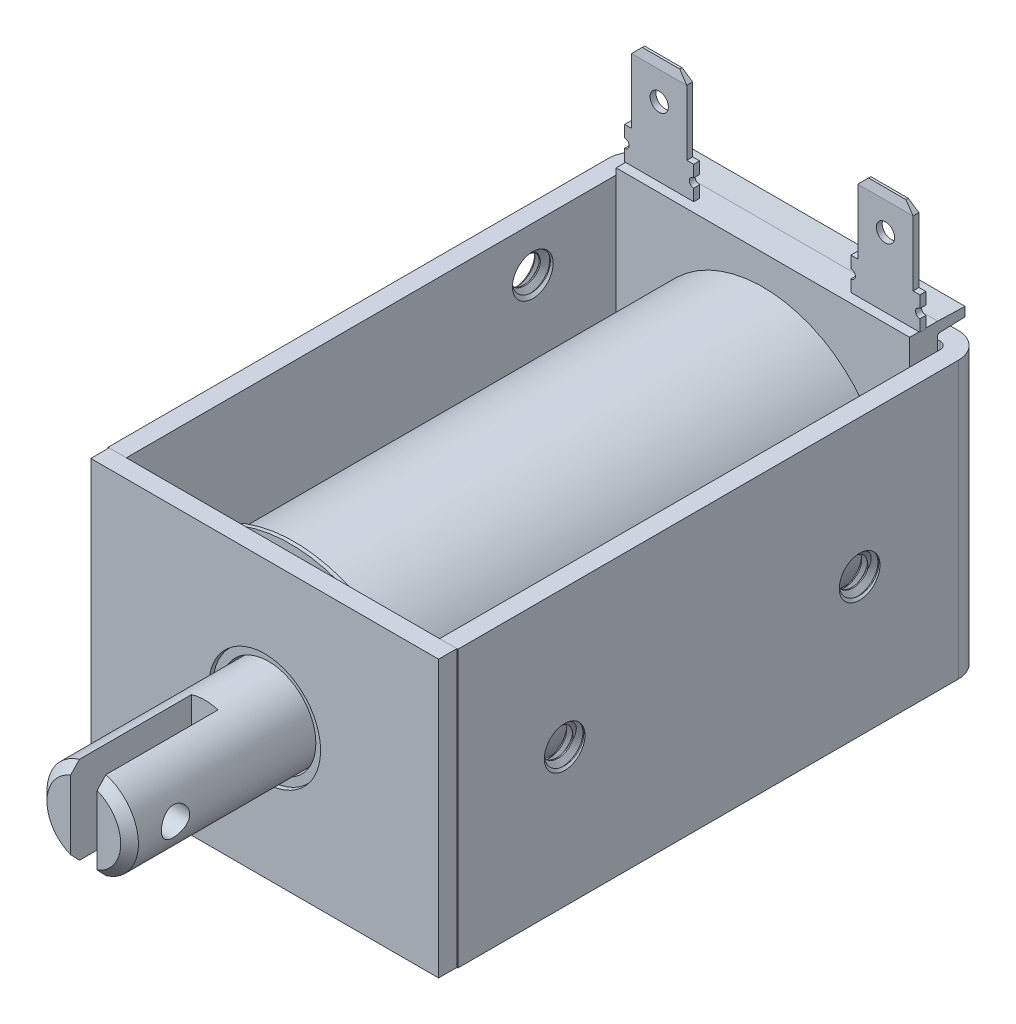
SolidWorks part; units mm, degrees
ref_plane "Front" through (0, 0, 0) normal (0, 0, 1) x (1, 0, 0)
ref_plane "Top" through (0, 0, 0) normal (0, 1, 0) x (1, 0, 0)
ref_plane "Right" through (0, 0, 0) normal (1, 0, 0) x (0, 0, -1)
sketch "Sketch1" plane through (0, 0, 0) normal (1, 0, 0) x (0, 0, -1)
  line L0 (0, 0) -> (46.8884, 0) construction
  line L1 (0, 0) -> (-15.5702, 0) construction
  line L2 (-15.5702, 3.937) -> (-15.5702, -3.937) construction
  line L4 (0, 11.8872) -> (0, -11.8872) construction
  line L6 (36.576, 8.0137) -> (36.576, 0) construction
  line L7 (15.9512, -8.0137) -> (15.9512, 0) construction
  circle A0 centre (36.576, 8.0137) radius 1.7526 construction
  circle A1 centre (15.9512, -8.0137) radius 1.7526 construction
  circle A2 centre (10.7696, 0) radius 1.7526 construction
  circle A3 centre (36.1696, 0) radius 1.7526 construction
  dimension "H" = 3.5052
  dimension "A" = 15.5702
  dimension "B" = 46.8884
  dimension "D" = 23.7744
  dimension "E" = 62.4586
  dimension "R" = 7.874
  dimension "G2" = 20.6248
  dimension "J1" = 16.0274
  dimension "K3" = 15.9512
  dimension "K4" = 10.3124
  dimension "G1" = 25.4
  dimension "K1" = 10.7696
  dimension "K2" = 10.7188
sketch "Sketch2" plane through (0, 0, 0) normal (0, 0, 1) x (1, 0, 0)
  line L0 (-14.9733, 0) -> (14.9733, 0) construction
  dimension "C" = 29.9466
sketch "Sketch3" plane through (0, 0, 0) normal (0, 1, 0) x (1, 0, 0)
  line L1 (-14.9733, 1.5748) -> (14.9733, 1.5748)
  line L2 (-14.9733, 1.5748) -> (-14.9733, 0)
  line L3 (-14.9733, 0) -> (14.9733, 0)
  line L4 (14.9733, 1.5748) -> (14.9733, 0)
  dimension "D1" = 1.5748
extrude "Boss-Extrude1" add sketch "Sketch3" along normal up to vertex (11.8872 mm away) and the other way up to vertex (11.8872 mm away) up to point (0, 11.8872, 0) other way up to point (0, -11.8872, 0)
sketch "Sketch4" plane through (0, 0, 0) normal (0, 0, -1) x (-1, 0, 0)
  circle A0 centre (0, 0) radius 4.8133
  dimension "D1" = 9.6266
extrude "Cut-Extrude1" cut sketch "Sketch4" along normal up to surface (1.5748 mm away) up to face at (0, 0, -1.5748)
sketch "Sketch5" plane through (0, 0, 0) normal (0, 1, 0) x (1, 0, 0)
  line L0 (-15.0622, 1.5748) -> (-15.0622, 44.6786)
  line L2 (-14.9733, 1.5748) -> (14.9733, 1.5748) construction
  line L5 (-12.8524, 46.8884) -> (12.8524, 46.8884)
  line L6 (15.0622, 44.6786) -> (15.0622, 1.5748)
  line L9 (15.0622, 1.5748) -> (13.4874, 1.5748)
  line L10 (13.4874, 1.5748) -> (13.4874, 44.6786)
  line L11 (12.8524, 45.3136) -> (-12.8524, 45.3136)
  line L12 (-13.4874, 44.6786) -> (-13.4874, 1.5748)
  line L13 (-13.4874, 1.5748) -> (-15.0622, 1.5748)
  line L14 (0, 46.8884) -> (0, 45.3136) construction
  arc A0 (-12.8524, 46.8884) -> (-15.0622, 44.6786) centre (-12.8524, 44.6786) ccw
  arc A1 (15.0622, 44.6786) -> (12.8524, 46.8884) centre (12.8524, 44.6786) ccw
  arc A2 (-12.8524, 45.3136) -> (-13.4874, 44.6786) centre (-12.8524, 44.6786) ccw
  arc A3 (13.4874, 44.6786) -> (12.8524, 45.3136) centre (12.8524, 44.6786) ccw
  dimension "D3" = 30.1244
  dimension "D1" = 2.2098
  dimension "D2" = 1.5748
extrude "Boss-Extrude2" add sketch "Sketch5" along normal up to vertex (11.8872 mm away) and the other way up to vertex (11.8872 mm away) separate body up to point (0, 11.8872, 0) other way up to point (0, -11.8872, 0)
sketch "Sketch6" plane through (0, 0, -46.8884) normal (0, 0, -1) x (-1, 0, 0)
  line L0 (14.9733, 0) -> (-14.9733, 0) construction
  circle A0 centre (0, 0) radius 2.1082
  dimension "D1" = 4.2164
extrude "Cut-Extrude2" cut sketch "Sketch6" against normal up to surface (1.5748 mm away) up to face at (0, 0, -45.3136)
sketch "Sketch7" plane through (0, 0, 0) normal (1, 0, 0) x (0, 0, -1)
  line L0 (36.1696, 0) -> (10.7696, 0) construction
  circle A0 centre (36.1696, 0) radius 1.7526 construction
  circle A3 centre (36.1696, 0) radius 1.7526
  dimension "D1" = 25.4
extrude "Boss-Extrude3" add sketch "Sketch7" along normal up to surface (1.5748 mm away) from surface at 13.4874 separate body up to face at (15.0622, 0, -23.1267) starting at face at (13.4874, 0, -23.1267)
sketch "Sketch8" plane through (13.4874, 0, 0) normal (-1, 0, 0) x (0, 0, 1)
  circle A1 centre (-36.1696, 0) radius 1.7526
  circle A2 centre (-36.1696, 0) radius 1.7526
  point P0 (-36.1696, 1.7526)
  dimension "D1" = 0
curve "Helix/Spiral1" pitch 0.7937 height 2.3177 turns 2.92 parameters "Pitch"=0.7937
ref_plane "Plane1" through (0, 0, -36.1696) normal (0, 0, 1) x (1, 0, 0)
sketch "Sketch9" plane through (0, 0, -36.1696) normal (0, 0, 1) x (1, 0, 0)
  line L0 (12.7433, 1.8385) -> (13.537, 1.8385) construction
  line L1 (13.537, 1.8385) -> (13.1401, 1.1511) construction
  line L2 (13.1401, 1.1511) -> (12.7433, 1.8385) construction
  line L3 (13.1897, 1.237) -> (13.0905, 1.237) construction
  line L4 (13.4874, 1.7526) -> (12.7929, 1.7526) construction
  line L5 (13.0905, 1.237) -> (13.1897, 1.237)
  line L6 (13.1897, 1.237) -> (13.5122, 1.7956)
  line L7 (13.5122, 1.7956) -> (12.7681, 1.7956)
  line L8 (12.7681, 1.7956) -> (13.0905, 1.237)
  line L9 (13.1401, 1.1511) -> (13.1401, 1.237) construction
  line L10 (13.1401, 1.7526) -> (13.1401, 1.8385) construction
  point P15 (13.1401, 1.7956)
  dimension "D1" = 0.7937
  dimension "D2" = 0.0992
sweep "Cut-Sweep1" cut profiles "Sketch9" path "Helix/Spiral1" align with end faces yes
sketch "Sketch10" plane through (13.4874, 0, 0) normal (-1, 0, 0) x (0, 0, 1)
  circle A1 centre (-36.1696, 0) radius 1.7526 construction
  circle A2 centre (-36.1696, 0) radius 1.7526
extrude "Boss-Extrude4" add sketch "Sketch10" against normal blind 0.7937 draft 45
sketch "Sketch11" plane through (15.0622, 0, 0) normal (1, 0, 0) x (0, 0, -1)
  circle A1 centre (36.1696, 0) radius 1.7526
  circle A2 centre (36.1696, 0) radius 1.7526
  dimension "D1" = 0
extrude "Boss-Extrude5" add sketch "Sketch11" against normal blind 0.7937 draft 45
pattern_linear "LPattern1" count 2 spacing 25.4 along (0, 0, 1) of bodies 165
sketch "Sketch20" plane through (0, 0, 0) normal (1, 0, 0) x (0, 0, -1)
  line L0 (36.576, 8.0137) -> (15.9512, -8.0137) construction
  circle A0 centre (36.576, 8.0137) radius 1.7526 construction
  circle A1 centre (36.576, 8.0137) radius 1.7526
  dimension "D1" = 26.1201
extrude "Boss-Extrude9" add sketch "Sketch20" against normal up to surface (1.5748 mm away) from surface at -13.4874 separate body up to face at (-15.0622, 0, -23.1267) starting at face at (-13.4874, 0, -23.1267)
sketch "Sketch21" plane through (-13.4874, 0, 0) normal (1, 0, 0) x (0, 0, -1)
  circle A1 centre (36.576, 8.0137) radius 1.7526
  circle A2 centre (36.576, 8.0137) radius 1.7526
  point P0 (36.576, 9.7663)
  dimension "D1" = 0
curve "Helix/Spiral2" pitch 0.7937 height 2.3685 turns 2.984 parameters "Pitch"=0.7937
ref_plane "Plane2" through (0, 0, -36.576) normal (0, 0, 1) x (1, 0, 0)
sketch "Sketch22" plane through (0, 0, -36.576) normal (0, 0, 1) x (1, 0, 0)
  line L0 (-13.537, 9.8522) -> (-12.7433, 9.8522) construction
  line L1 (-12.7433, 9.8522) -> (-13.1401, 9.1648) construction
  line L2 (-13.1401, 9.1648) -> (-13.537, 9.8522) construction
  line L3 (-13.1897, 9.2507) -> (-13.0905, 9.2507) construction
  line L4 (-13.4874, 9.7663) -> (-12.7929, 9.7663) construction
  line L5 (-13.1401, 9.1648) -> (-13.1401, 9.2507) construction
  line L6 (-13.1401, 9.7663) -> (-13.1401, 9.8522) construction
  line L7 (-13.1897, 9.2507) -> (-13.0905, 9.2507)
  line L8 (-13.0905, 9.2507) -> (-12.7681, 9.8093)
  line L9 (-12.7681, 9.8093) -> (-13.5122, 9.8093)
  line L10 (-13.5122, 9.8093) -> (-13.1897, 9.2507)
  point P13 (-13.1401, 9.8093)
  dimension "D1" = 0.7937
  dimension "D2" = 0.0992
sweep "Cut-Sweep2" cut profiles "Sketch22" path "Helix/Spiral2" align with end faces yes
sketch "Sketch23" plane through (-13.4874, 0, 0) normal (1, 0, 0) x (0, 0, -1)
  circle A1 centre (36.576, 8.0137) radius 1.7526
  circle A2 centre (36.576, 8.0137) radius 1.7526
  dimension "D1" = 0
extrude "Boss-Extrude10" add sketch "Sketch23" against normal blind 0.7937 draft 45
sketch "Sketch24" plane through (-15.0622, 0, 0) normal (-1, 0, 0) x (0, 0, 1)
  circle A1 centre (-36.576, 8.0137) radius 1.7526
  circle A2 centre (-36.576, 8.0137) radius 1.7526
  dimension "D1" = 0
extrude "Boss-Extrude11" add sketch "Sketch24" against normal blind 0.7937 draft 45
pattern_linear "LPattern2" count 2 spacing 26.1201 along (0, -0.6136, 0.7896) of bodies 186
combine bodies "Combine1" operation type subtract main body 133 bodies to subtract 165 178 187 186
sketch "Sketch12" plane through (0, 0, -45.3136) normal (0, 0, 1) x (1, 0, 0)
  line L0 (0, -11.8745) -> (0, 0) construction
  line L1 (-12.6365, 13.2715) -> (12.6365, 13.2715)
  line L2 (-12.6365, 13.2715) -> (-12.6365, -8.6995)
  line L3 (-9.4615, -11.8745) -> (9.4615, -11.8745)
  line L4 (12.6365, 13.2715) -> (12.6365, -8.6995)
  line L6 (-12.8524, -11.8872) -> (12.8524, -11.8872) construction
  circle A0 centre (0, 0) radius 4.0767
  arc A1 (-12.6365, -8.6995) -> (-9.4615, -11.8745) centre (-9.4615, -8.6995) ccw
  arc A2 (9.4615, -11.8745) -> (12.6365, -8.6995) centre (9.4615, -8.6995) ccw
  dimension "D2" = 8.1534
  dimension "D4" = 3.175
  dimension "D1" = 25.273
  dimension "D3" = 25.146
  dimension "D5" = 0.0127
extrude "Boss-Extrude6" add sketch "Sketch12" along normal blind 2.413 separate body
sketch "Sketch13" plane through (0, 0, 0) normal (1, 0, 0) x (0, 0, -1)
  line L0 (45.3136, 13.2715) -> (47.6758, 13.1952)
  line L1 (47.6758, 13.1952) -> (47.6758, 12.4078)
  line L2 (47.6758, 12.4078) -> (45.4611, 12.3363)
  line L3 (45.3136, 12.1839) -> (45.3136, 13.2715)
  line L4 (47.6758, 12.8015) -> (45.3136, 12.8015) construction
  arc A0 (45.4611, 12.3363) -> (45.3136, 12.1839) centre (45.466, 12.1839) ccw
  dimension "D1" = 0.1524
  dimension "D2" = 2.3622
  dimension "D3" = 3.7
  dimension "D4" = 1.85
  dimension "D5" = 0.7874
extrude "Boss-Extrude7" add sketch "Sketch13" along normal up to vertex (12.6365 mm away) and the other way up to vertex (12.6365 mm away) up to point (12.6365, 13.2715, -45.3136) other way up to point (-12.6365, 13.2715, -45.3136)
sketch "Sketch14" plane through (0, 0, 0) normal (1, 0, 0) x (0, 0, -1)
  line L0 (0, 0) -> (42.9006, 0) construction
  line L1 (0, 11.8872) -> (0, -11.8872) construction
  line L2 (42.9006, -8.6995) -> (42.9006, 13.2715) construction
  line L3 (42.9006, 4.0767) -> (42.9006, 10.7061)
  line L4 (42.9006, 10.7061) -> (2.54, 10.7061)
  line L5 (2.54, 10.7061) -> (2.54, 11.8999)
  line L6 (2.54, 11.8999) -> (2.2098, 11.8999)
  line L7 (2.2098, 11.8999) -> (2.2098, 9.525)
  line L8 (0.3302, 4.0767) -> (42.9006, 4.0767)
  line L12 (2.2098, 9.525) -> (1.905, 9.525)
  line L13 (1.905, 9.525) -> (1.905, 4.7663)
  line L14 (1.905, 4.7663) -> (0.3302, 4.7663)
  line L15 (0.3302, 4.7663) -> (0.3302, 4.0767)
  dimension "D1" = 40.3606
  dimension "D2" = 0.3302
  dimension "D3" = 0.3048
  dimension "D4" = 1.5748
  dimension "D5" = 21.4122
  dimension "D6" = 23.7998
  dimension "D7" = 19.05
  dimension "D8" = 9.5326
revolve "Revolve1" add sketch "Sketch14" angle 360 mid plane about L0
sketch "Sketch15" plane through (0, 0, -42.9006) normal (0, 0, 1) x (1, 0, 0)
  line L0 (12.6365, 13.2715) -> (-12.6365, 13.2715) construction
  line L1 (6.7691, 13.2715) -> (12.7127, 13.2715)
  line L2 (8.128, 22.4155) -> (7.366, 21.6535)
  line L3 (8.128, 22.4155) -> (11.3538, 22.4155)
  line L4 (12.7127, 13.2715) -> (12.7127, 14.2875)
  line L5 (0, 13.2715) -> (0, 22.4155) construction
  line L6 (7.366, 21.6535) -> (7.366, 16.0655)
  line L7 (7.366, 16.0655) -> (6.7691, 16.0655)
  line L8 (6.7691, 15.0495) -> (6.7691, 16.0655)
  line L9 (11.3538, 22.4155) -> (12.1158, 21.6535)
  line L10 (12.1158, 21.6535) -> (12.1158, 16.0655)
  line L11 (12.1158, 16.0655) -> (12.7127, 16.0655)
  line L12 (6.7691, 13.2715) -> (6.7691, 14.2875)
  line L13 (12.7127, 15.0495) -> (12.7127, 16.0655)
  line L14 (9.7409, 13.2715) -> (9.7409, 22.4155) construction
  line L15 (-12.7127, 13.2715) -> (-12.7127, 14.2875)
  line L16 (-12.7127, 15.0495) -> (-12.7127, 16.0655)
  line L17 (-12.1158, 16.0655) -> (-12.7127, 16.0655)
  line L18 (-12.1158, 21.6535) -> (-12.1158, 16.0655)
  line L19 (-11.3538, 22.4155) -> (-12.1158, 21.6535)
  line L20 (-8.128, 22.4155) -> (-11.3538, 22.4155)
  line L21 (-6.7691, 13.2715) -> (-6.7691, 14.2875)
  line L22 (-6.7691, 15.0495) -> (-6.7691, 16.0655)
  line L23 (-7.366, 16.0655) -> (-6.7691, 16.0655)
  line L24 (-7.366, 21.6535) -> (-7.366, 16.0655)
  line L25 (-8.128, 22.4155) -> (-7.366, 21.6535)
  line L26 (-6.7691, 13.2715) -> (-12.7127, 13.2715)
  line L27 (12.7127, 16.0655) -> (12.7127, 13.2715) construction
  arc A0 (6.7691, 15.0495) -> (6.7691, 14.2875) centre (6.7691, 14.6685) cw
  arc A1 (12.7127, 15.0495) -> (12.7127, 14.2875) centre (12.7127, 14.6685) ccw
  circle A2 centre (9.7409, 19.2405) radius 0.7874
  circle A3 centre (-9.7409, 19.2405) radius 0.7874
  arc A4 (-12.7127, 15.0495) -> (-12.7127, 14.2875) centre (-12.7127, 14.6685) cw
  arc A5 (-6.7691, 15.0495) -> (-6.7691, 14.2875) centre (-6.7691, 14.6685) ccw
  dimension "D3" = 1.5748
  dimension "D10" = 0.381
  dimension "D1" = 9.144
  dimension "D2" = 0.762
  dimension "D4" = 4.7498
  dimension "D5" = 0.762
  dimension "D6" = 5.9436
  dimension "D7" = 6.35
  dimension "D8" = 19.4818
  dimension "D9" = 3.175
extrude "Boss-Extrude8" add sketch "Sketch15" against normal blind 0.508 from offset 0.8128 offset against normal yes
sketch "Sketch16" plane through (0, 0, 0) normal (1, 0, 0) x (0, 0, -1)
  line L0 (43.7134, 22.4155) -> (43.7134, 21.6535)
  line L1 (43.7134, 21.6535) -> (43.8658, 22.4155)
  line L2 (44.2214, 22.4155) -> (43.7134, 22.4155) construction
  line L3 (43.8658, 22.4155) -> (43.7134, 22.4155)
  line L4 (44.069, 22.4155) -> (44.2214, 21.6535)
  line L5 (44.2214, 21.6535) -> (44.2214, 22.4155)
  line L6 (44.2214, 22.4155) -> (44.069, 22.4155)
  dimension "D1" = 0.1524
extrude "Cut-Extrude3" cut sketch "Sketch16" against normal through all and the other way through all
sketch "Sketch17" plane through (0, 0, 0) normal (1, 0, 0) x (0, 0, -1)
  line L0 (-15.5702, 0) -> (47.752, 0) construction
  line L1 (-15.5702, 0) -> (47.752, 0)
  line L2 (-15.5702, 0) -> (-15.5702, 3.175)
  line L3 (-14.8082, 3.937) -> (31.8262, 3.937)
  line L4 (47.752, 2.032) -> (47.752, 0)
  line L6 (45.212, 3.9751) -> (45.212, 2.032)
  line L7 (-14.8082, 3.937) -> (-15.5702, 3.175)
  line L8 (-14.8082, 3.937) -> (-15.5702, 3.937) construction
  line L9 (-15.5702, 3.937) -> (-15.5702, 3.175) construction
  line L10 (45.212, 2.032) -> (47.752, 2.032)
  line L11 (31.8262, 3.937) -> (31.8262, 3.9751)
  line L12 (31.8262, 3.9751) -> (45.212, 3.9751)
  dimension "D1" = 2.54
  dimension "D2" = 13.3858
  dimension "D3" = 0.762
  dimension "D4" = 63.3222
  dimension "D5" = 7.9502
  dimension "D6" = 4.064
revolve "Revolve2" add sketch "Sketch17" angle 360 mid plane about L0
sketch "Sketch18" plane through (0, 0, 0) normal (0, 1, 0) x (1, 0, 0)
  line L1 (-1.143, -15.5702) -> (1.143, -15.5702)
  line L2 (-1.143, -15.5702) -> (-1.143, -5.1562)
  line L3 (-1.143, -5.1562) -> (1.143, -5.1562)
  line L4 (1.143, -15.5702) -> (1.143, -5.1562)
  dimension "D1" = 2.286
  dimension "D2" = 10.414
extrude "Cut-Extrude4" cut sketch "Sketch18" along normal up to vertex (3.937 mm away) and the other way up to vertex (3.937 mm away) up to point (0, 3.937, 15.5702) other way up to point (0, -3.937, 15.5702)
sketch "Sketch19" plane through (0, 0, 0) normal (1, 0, 0) x (0, 0, -1)
  line L0 (-15.5702, 0) -> (-11.6078, 0) construction
  circle A0 centre (-11.6078, 0) radius 1.2192
  dimension "D1" = 2.4384
  dimension "D2" = 3.9624
extrude "Cut-Extrude5" cut sketch "Sketch19" against normal through all and the other way through all
sketch "SketchX" plane through (0, 0, 0) normal (1, 0, 0) x (0, 0, -1)
  line L2 (-28.2702, -2.9621) -> (-28.2702, 2.9621)
  line L13 (-15.5702, 0) -> (-11.6078, 0) construction
  line L15 (-28.2702, 2.9621) -> (-27.5082, 3.7674)
  line L16 (-17.8562, 3.937) -> (-5.1562, 3.937)
  line L17 (-28.2702, -2.9621) -> (-27.5082, -3.7674)
  line L18 (-17.8562, -3.937) -> (-5.1562, -3.937)
  line L26 (-27.5082, 3.7674) -> (-17.8562, 3.7674)
  line L27 (-17.8562, 3.7674) -> (-17.8562, 3.937)
  line L28 (-27.5082, -3.7674) -> (-17.8562, -3.7674)
  line L29 (-17.8562, -3.7674) -> (-17.8562, -3.937)
  line L30 (-24.3078, 0) -> (-28.2702, 0) construction
  line L32 (-14.8082, 3.7674) -> (-5.1562, 3.7674) construction
  line L33 (-5.1562, -3.7674) -> (-14.8082, -3.7674) construction
  line L35 (-5.1562, 3.937) -> (-5.1562, 3.7674) construction
  line L36 (31.8262, 3.937) -> (-5.1562, 3.937) construction
  circle A0 centre (-24.3078, 0) radius 1.2192
  circle A1 centre (-11.6078, 0) radius 1.2192 construction
  dimension "D1" = 0.762
  dimension "Stroke" = 12.7
equation "\"D1@Sketch9\" = \"Pitch@Helix/Spiral1\""
equation "\"D2@Sketch9\" = \"D1@Sketch9\" / 8"
equation "\"D3@LPattern1\" = \"D1@Sketch7\""
equation "\"D1@Sketch22\" = \"Pitch@Helix/Spiral2\""
equation "\"D2@Sketch22\" = \"D1@Sketch22\" / 8"
equation "\"D3@LPattern2\" = \"D1@Sketch20\""
